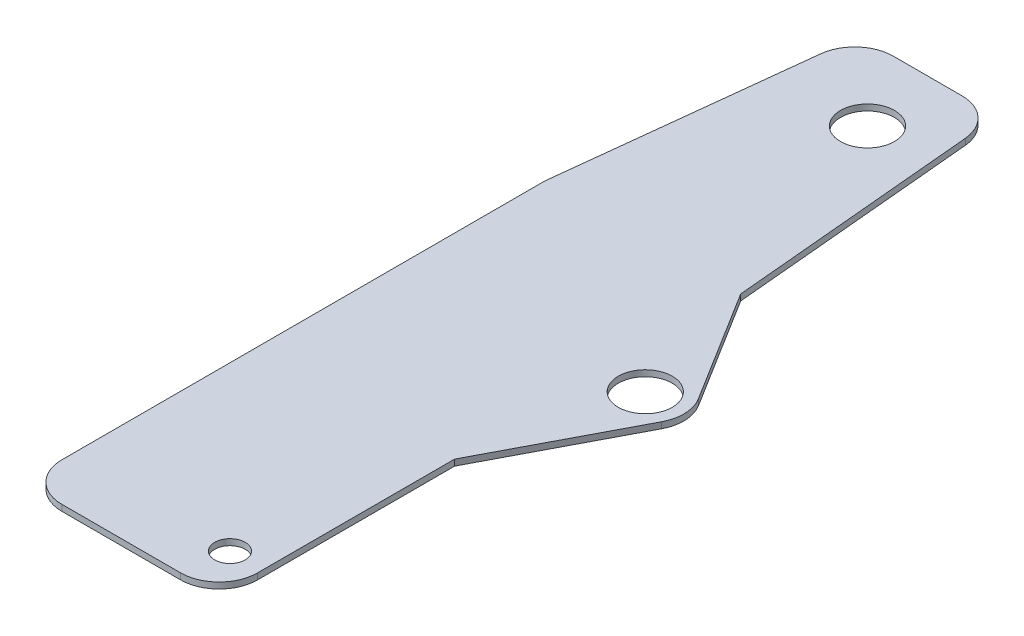
SolidWorks part; units mm, degrees
ref_plane "Front" through (0, 0, 0) normal (0, 0, 1) x (1, 0, 0)
ref_plane "Top" through (0, 0, 0) normal (0, 1, 0) x (1, 0, 0)
ref_plane "Right" through (0, 0, 0) normal (1, 0, 0) x (0, 0, -1)
sketch "Sketch1" plane through (0, 0, 0) normal (0, 1, 0) x (1, 0, 0)
  line L0 (10.4543, 228.6) -> (0, 135.3627)
  line L1 (0, 0) -> (50.8, 0)
  line L2 (0, 0) -> (0, 228.6)
  line L3 (0, 228.6) -> (50.8, 228.6)
  line L4 (50.8, 0) -> (50.8, 228.6)
  line L5 (42.3273, 228.6) -> (50.8, 135.3627)
  line L8 (50.8, 0) -> (24.327, 0)
  line L9 (50.8, 0) -> (50.8, -15)
  line L10 (50.8, -15) -> (24.327, -15)
  line L11 (24.327, 0) -> (24.327, -15)
  line L16 (50.8, 120.6192) -> (50.8, 104.4882)
  line L18 (50.8, 64.8791) -> (50.8, 87.4235)
  circle A3 centre (42.3273, 11.2956) radius 3.9601
  circle A12 centre (60.4, 101.001) radius 10
  circle A13 centre (29.5042, 189.5572) radius 7
  dimension "D3" = 20
  dimension "D5" = 15
  dimension "D6" = 14
  dimension "D1" = 50.8
  dimension "D2" = 228.6
extrude "Boss-Extrude1" add sketch "Sketch1" along normal blind 1.5875 contours L1 L4 L3 L0 L2 region at (25.4247, 0, -106.7072)
sketch "Sketch4" plane through (0, 0, -228.6) normal (0, 0, -1) x (-1, 0, 0)
  line L1 (-61.3109, 11.9192) -> (4.9615, 11.9192)
  line L2 (-61.3109, 11.9192) -> (-61.3109, -15.8811)
  line L3 (-61.3109, -15.8811) -> (4.9615, -15.8811)
  line L4 (4.9615, 11.9192) -> (4.9615, -15.8811)
extrude "Cut-Extrude2" cut sketch "Sketch4" against normal blind 20
fillet "Fillet3" radius 10 1 edges at (44.1447, 0.7937, -208.6)
fillet "Fillet4" radius 10 3 edges at (50.8, 0.7937, 0) (0, 0.7937, 0) (8.2118, 0.7937, -208.6)
sketch "Sketch6" plane through (0, 1.5875, 0) normal (0, 1, 0) x (1, 0, 0)
  line L0 (68.8909, 106.2834) -> (50.8, 135.3627)
  line L1 (50.8, 135.3627) -> (50.8, 103.801)
  line L2 (69.2582, 96.3607) -> (50.8, 61.1242)
  line L3 (50.8, 10) -> (50.8, 98.201) construction
  line L4 (50.8, 61.1242) -> (50.8, 96.3607)
  line L5 (50.8, 96.3607) -> (50.8, 98.201)
  circle A0 centre (60.4, 101.001) radius 10
  line M4 (50.8, 10) -> (50.8, 98.201)
  arc M5 (50.8, 98.201) -> (50.8, 103.801) centre (60.4, 101.001) cw
  line M6 (50.8, 103.801) -> (50.8, 135.3627)
extrude "Boss-Extrude3" add sketch "Sketch6" against normal blind 1.5875 contours A0 L0 M6 | A0 M5 | A0 L2 M4 region at (55.8248, 1.5875, -118.0301) region at (60.4, 1.5875, -101.001) region at (56.0341, 1.5875, -82.1407)
sketch "Sketch7" plane through (0, 1.5875, 0) normal (0, 1, 0) x (1, 0, 0)
  circle A0 centre (60.4, 101.001) radius 7
  dimension "D1" = 14
extrude "Cut-Extrude3" cut sketch "Sketch7" against normal blind 1.5875
equation "\"7i\"=101.6"
